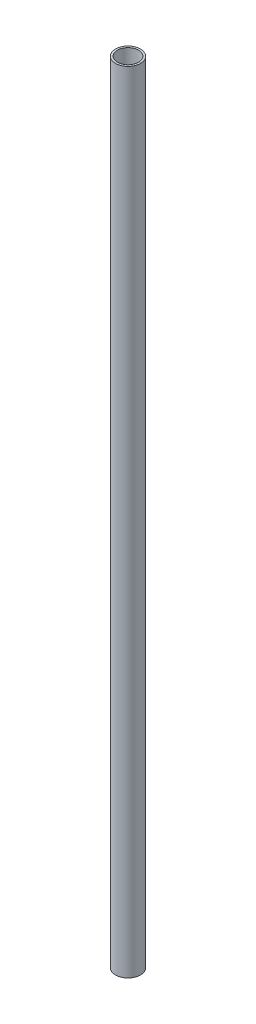
SolidWorks part; units mm, degrees
note: '?' marks a value the reader was unsure of.
material "AISI 4130 Steel, annealed at 865C"
ref_plane "Front Plane" through (0, 0, 0) normal (0, 0, 1) x (1, 0, 0)
ref_plane "Top Plane" through (0, 0, 0) normal (0, 1, 0) x (1, 0, 0)
ref_plane "Right Plane" through (0, 0, 0) normal (1, 0, 0) x (0, 0, -1)
sketch "Sketch1" plane through (0, 0, 0) normal (0, 1, 0) x (1, 0, 0)
  circle A0 centre (0, 0) radius 6.6929
  circle A1 centre (0, 0) radius 7.9375
  dimension "D1" = 15.875
  dimension "D2" = 13.3858
extrude "Boss-Extrude1" add sketch "Sketch1" along normal blind 501.65
ref_axis "Axis1" through (0, 501.65, 0) along (0, -1, 0)?
